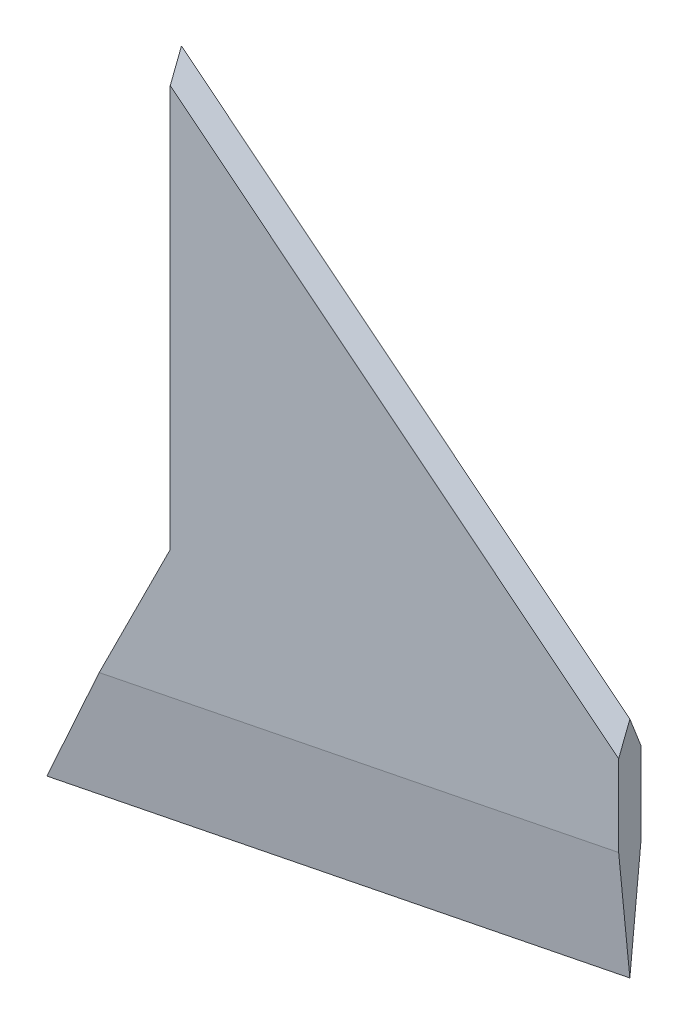
SolidWorks part; units mm, degrees
ref_plane "Front Plane" through (0, 0, 0) normal (0, 0, 1) x (1, 0, 0)
ref_plane "Top Plane" through (0, 0, 0) normal (0, 1, 0) x (1, 0, 0)
ref_plane "Right Plane" through (0, 0, 0) normal (1, 0, 0) x (0, 0, -1)
sketch "Sketch1" plane through (0, 0, 0) normal (0, 0, 1) x (1, 0, 0)
  line L0 (0, 0) -> (0, 150)
  line L1 (0, 150) -> (100, 70)
  line L2 (100, 70) -> (100, 20)
  line L3 (100, 20) -> (0, 0)
  line L4 (-30, -6) -> (0, 0)
  line L5 (-30, -6) -> (0, 54)
  line L6 (0, 54) -> (0, 0)
  point P5 (0, 75)
  point P7 (100, 45)
  point P9 (0, 66.5453)
  point P10 (0, 96.2918)
  dimension "Root Chord Length" = 150
  dimension "Tip Chord Length" = 50
  dimension "Fin Length" = 100
  dimension "Taper Offset Distance" = 30
  dimension "D1" = 30
  dimension "D2" = 60
extrude "Boss-Extrude1" add sketch "Sketch1" along normal blind 5 contours L5 L4 L0 | L3 L2 L1 L0 region at (-10, 16, 0) region at (41.6667, 62.5, 0)
chamfer "Chamfer6" distance 5 distance2 2.5 1 edges at (50, 110, 5) first distance on face at (34, 57.6, 5)
chamfer "Chamfer7" distance 2.5 distance2 5 1 edges at (50, 110, 0) first distance on face at (50, 110, 1.25)
chamfer "Chamfer8" distance 2.5 distance2 25 1 edges at (35, 7, 5) first distance on face at (35, 7, 2.5)
chamfer "Chamfer9" distance 25 distance2 2.5 1 edges at (35, 7, 0) first distance on face at (34, 55.0388, 0)
equation "\"Root Chord Length\" = 150"
equation "\"Tip Chord Length\" = 50"
equation "\"Fin Length\"= 100"
equation "\"Taper Offset Distance\"= 30"
equation "\"Root Chord Length@Sketch1\"= \"Root Chord Length\""
equation "\"Tip Chord Length@Sketch1\"= \"Tip Chord Length\""
equation "\"Fin Length@Sketch1\"= \"Fin Length\""
equation "\"Fin Thickness\"= 5"
equation "\"D1@Boss-Extrude1\"= \"Fin Thickness\""
equation "\"Leading Edge Taper Distance\"= 5"
equation "\"Taper Offset Distance@Sketch1\"= \"Taper Offset Distance\""
equation "\"Trailing Edge Taper Distance\"= 25"
equation "\"D1@Chamfer6\"= \"Leading Edge Taper Distance\""
equation "\"D3@Chamfer6\"= \"Fin Thickness\" / 2"
equation "\"D3@Chamfer7\"= \"Leading Edge Taper Distance\""
equation "\"D1@Chamfer7\"= \"Fin Thickness\" / 2"
equation "\"D3@Chamfer8\"= \"Trailing Edge Taper Distance\""
equation "\"D1@Chamfer8\"= \"Fin Thickness\" / 2"
equation "\"D1@Chamfer9\"= \"Trailing Edge Taper Distance\""
equation "\"D3@Chamfer9\"= \"Fin Thickness\" / 2"
equation "\"Boat Tail Taper Length\"= 60"
equation "\"Boat Tail Taper Distance\"= 30"
equation "\"D2@Sketch1\"= \"Boat Tail Taper Length\""
equation "\"D1@Sketch1\"= \"Boat Tail Taper Distance\""
